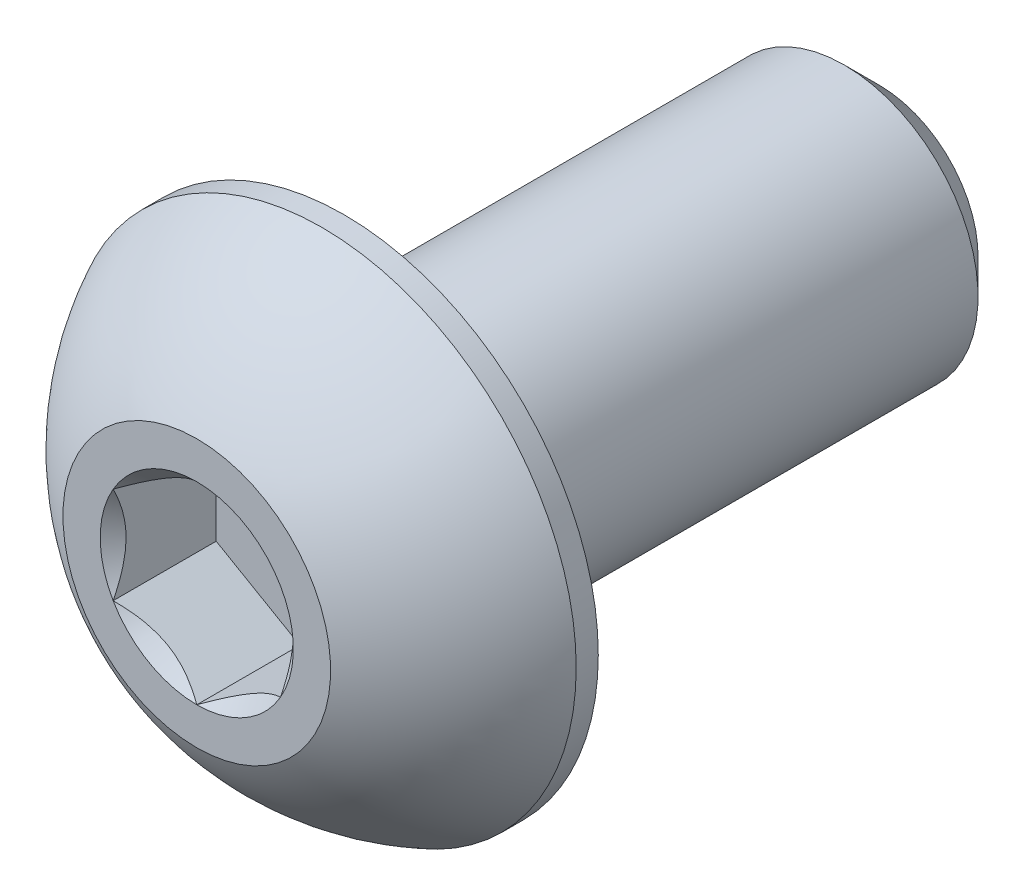
SolidWorks part; units mm, degrees
ref_plane "Front" through (0, 0, 0) normal (0, 0, 1) x (1, 0, 0)
ref_plane "Top" through (0, 0, 0) normal (0, 1, 0) x (1, 0, 0)
ref_plane "Right" through (0, 0, 0) normal (1, 0, 0) x (0, 0, -1)
sketch "Sketch1" plane through (0, 0, 0) normal (1, 0, 0) x (0, 0, -1)
  line L2 (2.2, 2) -> (10.2, 2)
  line L3 (10.2, 2) -> (10.2, 0)
  line L4 (10.2, 0) -> (2.2, 0)
  line L6 (1.87, 3.8) -> (2.2, 3.8) construction
  line L7 (10.2, 2) -> (10.2, -2) construction
  line L8 (0, 0) -> (2.2, 0) construction
  line L9 (2.2, 3.8) -> (2.2, -3.8) construction
  line L11 (2.2, 2) -> (2.2, 0)
  line L13 (0, 1.25) -> (0, -1.25) construction
  line L14 (0, 1.25) -> (0, 2) construction
  arc A3 (0, 2) -> (1.87, 3.8) centre (3.7264, 0) cw construction
  dimension "D1" = 0.33
revolve "Revolve1" add sketch "Sketch1" angle 360 mid plane about L4
sketch "Sketch3" plane through (0, 0, -10.2) normal (0, 0, -1) x (-1, 0, 0)
  circle A0 centre (0, 0) radius 2
curve "Helix/Spiral1" pitch 0.7 height 8.7 turns 12.4286
sketch "Sketch2" plane through (0, 0, 0) normal (1, 0, 0) x (0, 0, -1)
  line L0 (10.2, 2) -> (10.8125, 2)
  line L1 (10.8125, 2) -> (10.55, 1.5453)
  line L2 (10.55, 1.5453) -> (10.4625, 1.5453)
  line L3 (10.4625, 1.5453) -> (10.2, 2)
  line L4 (10.3313, 1.7727) -> (10.6813, 1.7727) construction
  dimension "D1" = 60
  dimension "D2" = 0.0875
  dimension "D3" = 0.35
chamfer "Chamfer1" distance 0.525 angle 45 1 edges at (0, 2, -10.2)
sweep "Cut-Sweep1" [suppressed] cut profiles "Sketch2" path "Helix/Spiral1"
sketch "Sketch7" plane through (0, 0, 0) normal (1, 0, 0) x (0, 0, -1)
  line L6 (1.87, 3.8) -> (2.2, 3.8) construction
  line L8 (0, 0) -> (2.2, 0) construction
  line L11 (2.2, 3.8) -> (2.2, -3.8) construction
  line L12 (1.87, 3.8) -> (2.2, 3.8)
  line L13 (0, 0) -> (2.2, 0)
  line L14 (0, 1.25) -> (0, -1.25) construction
  line L15 (2.2, 3.8) -> (2.2, 0)
  line L16 (0, 2) -> (0, 0)
  arc A2 (1.87, 3.8) -> (0, 2) centre (3.7264, 0) ccw construction
  arc A3 (1.87, 3.8) -> (0, 2) centre (3.7264, 0) ccw
revolve "Revolve2" add sketch "Sketch7" angle 360 mid plane about L13
sketch "Sketch5" plane through (0, 0, 0) normal (0, 0, 1) x (1, 0, 0)
  line L1 (1.25, -0.7217) -> (1.25, 0.7217)
  line L2 (1.25, 0.7217) -> (0, 1.4434)
  line L3 (0, 1.4434) -> (-1.25, 0.7217)
  line L4 (-1.25, 0.7217) -> (-1.25, -0.7217)
  line L5 (-1.25, -0.7217) -> (0, -1.4434)
  line L6 (0, -1.4434) -> (1.25, -0.7217)
  circle A0 centre (0, 0) radius 1.25 construction
extrude "Cut-Extrude2" cut sketch "Sketch5" against normal blind 1.54
sketch "Sketch6" plane through (0, 0, 0) normal (0, 0, 1) x (1, 0, 0)
  circle A0 centre (0, 0) radius 1.4434
extrude "Cut-Extrude3" cut sketch "Sketch6" against normal blind 1.54 draft 45
sketch "Sketch9" [suppressed] plane through (0, 0, -5.0546) normal (0, 0, 1) x (1, 0, 0)
  circle A2 centre (0, 0) radius 4.7625
extrude "Boss-Extrude2" [suppressed] add sketch "Sketch9" against normal offset from surface (6.35 mm away) 31.75
sketch "Sketch10" plane through (0, 0, 0) normal (1, 0, 0) x (0, 0, -1)
  line L0 (10.2, 2) -> (10.2, -2) construction
  point P0 (9.15, -2)
  dimension "D1" = 1.05
equation "\"D3@Helix/Spiral1\" = \"Lg@Sketch1\" + \"D4@Helix/Spiral1\""
equation "\"D2@Sketch2\" = \"D4@Helix/Spiral1\" * .125"
equation "\"D3@Sketch2\" = \"D4@Helix/Spiral1\" * .5"
equation "\"D1@Chamfer1\" = \"D4@Helix/Spiral1\" * .75"
equation "\"D1@Cut-Extrude2\" = \"Head Ht@Sketch1\" * .7"
equation "\"D1@Sketch1\" = \"Head Ht@Sketch1\" * .15"
equation "\"D1@Sketch10\" = \"D4@Helix/Spiral1\" * 1.5"
equation "\"D1@Cut-Extrude3\" = \"D1@Cut-Extrude2\""
